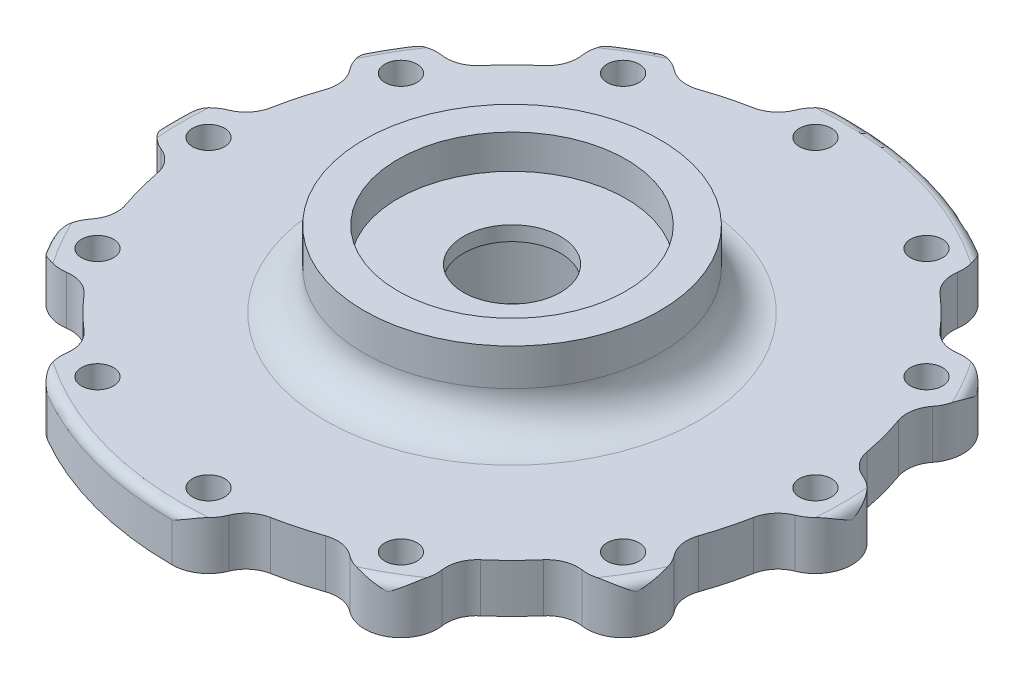
SolidWorks part; units mm, degrees
ref_plane "Front Plane" through (0, 0, 0) normal (0, 0, 1) x (1, 0, 0)
ref_plane "Top Plane" through (0, 0, 0) normal (0, 1, 0) x (1, 0, 0)
ref_plane "Right Plane" through (0, 0, 0) normal (1, 0, 0) x (0, 0, -1)
sketch "Sketch1" plane through (0, 0, 0) normal (0, 0, 1) x (1, 0, 0)
  line L1 (-70, -26.6983) -> (-45, -26.6983)
  line L18 (-45, -26.6983) -> (-45, -31.6983)
  line L19 (-45, -31.6983) -> (-40, -31.6983)
  line L23 (0, 95.7864) -> (0, -110.3116) construction
  line L28 (-70, -26.6983) -> (-70, -18.6983)
  line L29 (-68, -16.6983) -> (-38.5, -16.6983)
  line L30 (-30.5, -8.6983) -> (-30.5, -1.0983)
  line L31 (-30.5, -1.0983) -> (-23.5, -1.0983)
  line L32 (-23.5, -1.0983) -> (-23.5, -8.0983)
  line L40 (-23.5, -11.0983) -> (-10, -11.0983)
  line L41 (-10, -11.0983) -> (-10, -8.0983)
  line L42 (-10, -8.0983) -> (-23.5, -8.0983)
  line L43 (-23.5, -11.0983) -> (-23.5, -31.6983)
  line L44 (-40, -31.6983) -> (-23.5, -31.6983)
  arc A1 (-30.5, -8.6983) -> (-38.5, -16.6983) centre (-38.5, -8.6983) cw
  arc A2 (-70, -18.6983) -> (-68, -16.6983) centre (-68, -18.6983) cw
  point P31 (-70, -16.6983)
  dimension "D1" = 45
  dimension "D10" = 20
  dimension "D2" = 8
  dimension "D7" = 7
  dimension "D13" = 2
  dimension "D3" = 7
  dimension "D4" = 10
  dimension "D5" = 5
  dimension "D6" = 20.6
  dimension "D8" = 47
  dimension "D11" = 3
revolve "Revolve1" add sketch "Sketch1" angle 360 about L23
sketch "Sketch2" plane through (0, -16.6983, 0) normal (0, 1, 0) x (1, 0, 0)
  circle A0 centre (0, 0) radius 62.5 construction
  point P0 (0, 0)
  point P3 (31.25, -54.1266)
  point P7 (0, -62.5)
  point P8 (-31.25, -54.1266)
  point P9 (-54.1266, -31.25)
  point P10 (-62.5, 0)
  point P11 (-54.1266, 31.25)
  point P12 (-31.25, 54.1266)
  point P13 (0, 62.5)
  point P14 (31.25, 54.1266)
  point P15 (54.1266, 31.25)
  point P16 (62.5, 0)
  point P17 (54.1266, -31.25)
  point P18 (0, 0)
  dimension "D1" = 125
  dimension "D2" = 12
sketch "Sketch4" plane through (0, -16.6983, 0) normal (0, 1, 0) x (1, 0, 0)
  circle A0 centre (0, 0) radius 62.5 construction
  point P3 (0, 62.5)
  point P7 (31.25, 54.1266)
  point P8 (54.1266, 31.25)
  point P9 (62.5, 0)
  point P10 (54.1266, -31.25)
  point P11 (31.25, -54.1266)
  point P12 (0, -62.5)
  point P13 (-31.25, -54.1266)
  point P14 (-54.1266, -31.25)
  point P15 (-62.5, 0)
  point P16 (-54.1266, 31.25)
  point P17 (-31.25, 54.1266)
  dimension "D1" = 125
hole_wizard "M6 Clearance Hole1" positions "Sketch4" profile "Sketch5" hole size "M6" standard "ANSI Metric" end condition through all
sketch "Sketch5" plane through (-31.25, -16.6983, -54.1266) normal (1, 0, 0) x (0, 0, 1)
  line L0 (0, 0) -> (0, 15)
  line L1 (0, 15) -> (3.3, 15)
  line L2 (3.3, 15) -> (3.3, 0)
  line L5 (3.3, 0) -> (0, 0)
  line L11 (0, -6.35) -> (0, 107.95) construction
  dimension "Thru Hole Dia." = 6.6
  dimension "Thru Hole Depth" = 15
hole_wizard "M6 Clearance Hole2" positions "Sketch2" profile "Sketch3" hole size "M6" standard "ANSI Metric" end condition through all
sketch "Sketch3" plane through (0, -16.6983, 0) normal (1, 0, 0) x (0, 0, 1)
  line L0 (0, 0) -> (0, 15)
  line L1 (0, 15) -> (3.3, 15)
  line L2 (3.3, 15) -> (3.3, 0)
  line L5 (3.3, 0) -> (0, 0)
  line L11 (0, -6.35) -> (0, 107.95) construction
  dimension "Thru Hole Dia." = 6.6
  dimension "Thru Hole Depth" = 15
sketch "Sketch6" plane through (0, -16.6983, 0) normal (0, 1, 0) x (1, 0, 0)
  arc A0 (-65.2823, 6.9648) -> (-65.2823, -6.9648) centre (-62.5, 0) ccw
  arc A1 (-61.3998, -11.6755) -> (-65.2823, -6.9648) centre (-67.638, -12.8617) ccw
  arc A2 (-61.3998, -11.6755) -> (-59.0115, -20.5886) centre (0, 0) ccw
  arc A3 (-60.0186, -26.6094) -> (-59.0115, -20.5886) centre (-65.0071, -22.6804) ccw
  arc A4 (-60.0186, -26.6094) -> (-53.0537, -38.6729) centre (-54.1266, -31.25) ccw
  arc A5 (-47.336, -40.8112) -> (-53.0537, -38.6729) centre (-52.1454, -44.9576) ccw
  arc A6 (-47.336, -40.8112) -> (-40.8112, -47.336) centre (0, 0) ccw
  arc A7 (-38.6729, -53.0537) -> (-40.8112, -47.336) centre (-44.9576, -52.1454) ccw
  arc A8 (-38.6729, -53.0537) -> (-35, -60.6218) centre (-31.25, -54.1266) ccw
  arc A9 (-35, -60.6218) -> (0, -70) centre (0, 0) ccw
  arc A10 (0, -70) -> (6.9648, -65.2823) centre (0, -62.5) ccw
  arc A11 (11.6755, -61.3998) -> (6.9648, -65.2823) centre (12.8617, -67.638) ccw
  arc A12 (11.6755, -61.3998) -> (20.5886, -59.0115) centre (0, 0) ccw
  arc A13 (26.6094, -60.0186) -> (20.5886, -59.0115) centre (22.6804, -65.0071) ccw
  arc A14 (26.6094, -60.0186) -> (38.6729, -53.0537) centre (31.25, -54.1266) ccw
  arc A15 (40.8112, -47.336) -> (38.6729, -53.0537) centre (44.9576, -52.1454) ccw
  arc A16 (40.8112, -47.336) -> (47.336, -40.8112) centre (0, 0) ccw
  arc A17 (53.0537, -38.6729) -> (47.336, -40.8112) centre (52.1454, -44.9576) ccw
  arc A18 (53.0537, -38.6729) -> (60.0186, -26.6094) centre (54.1266, -31.25) ccw
  arc A19 (59.0115, -20.5886) -> (60.0186, -26.6094) centre (65.0071, -22.6804) ccw
  arc A20 (59.0115, -20.5886) -> (61.3998, -11.6755) centre (0, 0) ccw
  arc A21 (65.2823, -6.9648) -> (61.3998, -11.6755) centre (67.638, -12.8617) ccw
  arc A22 (65.2823, -6.9648) -> (65.2823, 6.9648) centre (62.5, 0) ccw
  arc A23 (61.3998, 11.6755) -> (65.2823, 6.9648) centre (67.638, 12.8617) ccw
  arc A24 (61.3998, 11.6755) -> (59.0115, 20.5886) centre (0, 0) ccw
  arc A25 (60.0186, 26.6094) -> (59.0115, 20.5886) centre (65.0071, 22.6804) ccw
  arc A26 (60.0186, 26.6094) -> (53.0537, 38.6729) centre (54.1266, 31.25) ccw
  arc A27 (47.336, 40.8112) -> (53.0537, 38.6729) centre (52.1454, 44.9576) ccw
  arc A28 (47.336, 40.8112) -> (40.8112, 47.336) centre (0, 0) ccw
  arc A29 (38.6729, 53.0537) -> (40.8112, 47.336) centre (44.9576, 52.1454) ccw
  arc A30 (38.6729, 53.0537) -> (35, 60.6218) centre (31.25, 54.1266) ccw
  arc A31 (35, 60.6218) -> (0, 70) centre (0, 0) ccw
  arc A32 (0, 70) -> (-6.9648, 65.2823) centre (0, 62.5) ccw
  arc A33 (-11.6755, 61.3998) -> (-6.9648, 65.2823) centre (-12.8617, 67.638) ccw
  arc A34 (-11.6755, 61.3998) -> (-20.5886, 59.0115) centre (0, 0) ccw
  arc A35 (-26.6094, 60.0186) -> (-20.5886, 59.0115) centre (-22.6804, 65.0071) ccw
  arc A36 (-26.6094, 60.0186) -> (-38.6729, 53.0537) centre (-31.25, 54.1266) ccw
  arc A37 (-40.8112, 47.336) -> (-38.6729, 53.0537) centre (-44.9576, 52.1454) ccw
  arc A38 (-40.8112, 47.336) -> (-47.336, 40.8112) centre (0, 0) ccw
  arc A39 (-53.0537, 38.6729) -> (-47.336, 40.8112) centre (-52.1454, 44.9576) ccw
  arc A40 (-53.0537, 38.6729) -> (-60.0186, 26.6094) centre (-54.1266, 31.25) ccw
  arc A41 (-59.0115, 20.5886) -> (-60.0186, 26.6094) centre (-65.0071, 22.6804) ccw
  arc A42 (-59.0115, 20.5886) -> (-61.3998, 11.6755) centre (0, 0) ccw
  arc A43 (-65.2823, 6.9648) -> (-61.3998, 11.6755) centre (-67.638, 12.8617) ccw
  circle A45 centre (0, 0) radius 70
  circle M46 centre (31.25, 54.1266) radius 3.3
  circle M47 centre (54.1266, 31.25) radius 3.3
  circle M48 centre (62.5, 0) radius 3.3
  circle M49 centre (54.1266, -31.25) radius 3.3
  circle M50 centre (31.25, -54.1266) radius 3.3
  circle M52 centre (-31.25, -54.1266) radius 3.3
  circle M53 centre (-54.1266, -31.25) radius 3.3
  circle M54 centre (-62.5, 0) radius 3.3
  circle M55 centre (-54.1266, 31.25) radius 3.3
  circle M56 centre (-31.25, 54.1266) radius 3.3
  circle M57 centre (0, 0) radius 68
extrude "Cut-Extrude1" cut sketch "Sketch6" against normal through all contours A32 A45 A36 M57 | A36 A35 A34 A33 A32 M56 M57 | A30 A29 A28 A27 A26 M46 M57 | A26 A45 A30 M57 | A26 A25 A24 A23 A22 M47 M57 | A22 A45 A26 M57 | A22 A21 A20 A19 A18 M48 M57 | A18 A45 A22 M57 | A14 A45 A18 M57 | A18 A17 A16 A15 A14 M49 M57 | A14 A13 A12 A11 A10 M50 M57 | A10 A45 A14 M57 | A8 A7 A6 A5 A4 M52 M57 | A4 A45 A8 M57 | A0 A45 A4 M57 | A4 A3 A2 A1 A0 M53 M57 | A40 A39 A38 A37 A36 M55 M57 | A36 A45 A40 M57 | A0 A43 A42 A41 A40 M54 M57 | A40 A45 A0 M57 region at (-63.0463, -16.6983, -16.8932) region at (-66.2068, -16.6983, -17.74) region at (-66.2068, -16.6983, 17.74) region at (-63.0463, -16.6983, 16.8932) region at (-48.4667, -16.6983, -48.4667) region at (-48.4667, -16.6983, 48.4667) region at (-46.1531, -16.6983, -46.1531) region at (-17.74, -16.6983, -66.2068) region at (-46.1531, -16.6983, 46.1531) region at (-16.8932, -16.6983, -63.0463) region at (17.74, -16.6983, 66.2068) region at (48.4667, -16.6983, -48.4667) region at (16.8932, -16.6983, 63.0463) region at (48.4667, -16.6983, 48.4667) region at (46.1531, -16.6983, -46.1531) region at (66.2068, -16.6983, -17.74) region at (46.1531, -16.6983, 46.1531) region at (66.2068, -16.6983, 17.74) region at (63.0463, -16.6983, -16.8932) region at (63.0463, -16.6983, 16.8932)
sketch "Sketch7" plane through (0, -16.6983, 0) normal (0, 1, 0) x (1, 0, 0)
  line L0 (-27.5, 47.6314) -> (-19.25, 33.342)
  line L1 (0, 38.5) -> (0, 55)
  line L2 (-30.0571, 46.0605) -> (-21.8481, 31.842)
  line L3 (3, 38.5) -> (3, 54.9181)
  line L4 (-30.0981, 46.1314) -> (-21.8481, 31.842) construction
  line L5 (3, 38.5) -> (3, 55) construction
  line L6 (0, 0) -> (0, 38.5) construction
  line L7 (0, 0) -> (-19.25, 33.342) construction
  line L8 (37.5427, 9.044) -> (53.1573, 14.1175)
  line L9 (36.6157, 11.8972) -> (52.3081, 16.9959)
  line L10 (36.8022, 40.873) -> (25.7615, 28.6111)
  line L11 (34.518, 42.8195) -> (23.5321, 30.6185)
  line L12 (20.2027, -32.9105) -> (29.853, -46.193)
  line L13 (22.6297, -31.1472) -> (32.3282, -44.4959)
  line L14 (50.245, -22.3705) -> (35.1715, -15.6594)
  line L15 (51.3904, -19.5966) -> (36.3917, -12.9187)
  line L16 (-25.0568, -29.3838) -> (-34.7071, -42.6663)
  line L17 (-22.6297, -31.1472) -> (-32.3282, -44.4959)
  line L18 (-5.7491, -54.6987) -> (-4.0243, -38.2891)
  line L19 (-2.7569, -54.9309) -> (-1.0408, -38.6027)
  line L20 (-35.6886, 14.7503) -> (-51.3032, 19.8238)
  line L21 (-36.6157, 11.8972) -> (-52.3081, 16.9959)
  line L22 (-53.7981, -11.4351) -> (-37.6587, -8.0046)
  line L23 (-53.0943, -14.3526) -> (-37.0349, -10.939)
  circle A0 centre (0, 0) radius 38.5
  circle A1 centre (0, 0) radius 55
  point P49 (0, 0)
  dimension "D1" = 110
  dimension "D5" = 77
  dimension "D3" = 30
  dimension "D4" = 30
  dimension "D2" = 3
  dimension "D6" = 5
extrude "Cut-Extrude2" [suppressed] cut sketch "Sketch7" against normal blind 5 contours L1 A1 L0 A0 | L10 A1 L1 A0 | L9 A1 L10 A0 | L14 A1 L9 A0 | L13 A1 L14 A0 | A1 L13 A0 L18 | L17 A1 L18 A0 | L22 A1 L17 A0 | L21 A1 L22 A0 | L0 A1 L21 A0
